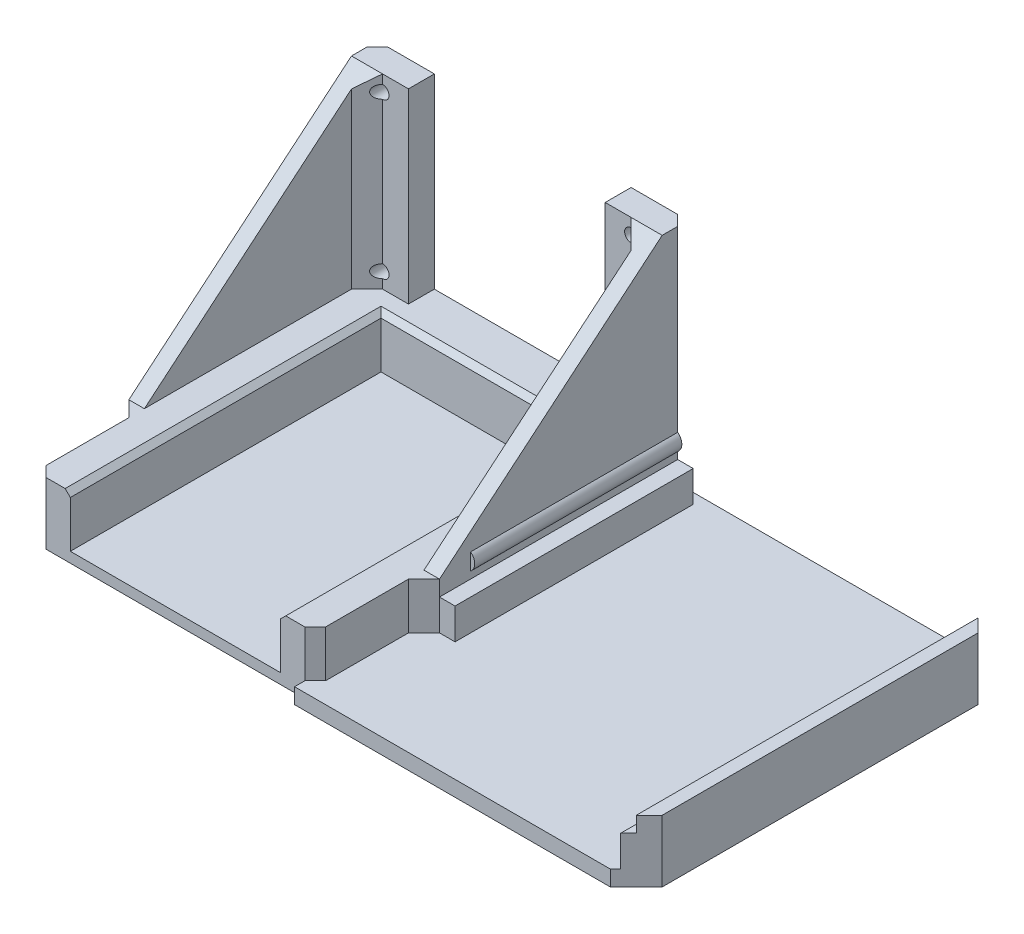
SolidWorks part; units mm, degrees
material "ABS"
ref_plane "Front Plane" through (0, 0, 0) normal (0, 0, 1) x (1, 0, 0)
ref_plane "Top Plane" through (0, 0, 0) normal (0, 1, 0) x (1, 0, 0)
ref_plane "Right Plane" through (0, 0, 0) normal (1, 0, 0) x (0, 0, -1)
sketch "Sketch1" plane through (0, 0, 0) normal (0, 0, 1) x (1, 0, 0)
  line L0 (-3, -3) -> (-3, 33)
  line L1 (0, 0) -> (5, 0) construction
  line L2 (0, 0) -> (0, 30) construction
  line L3 (0, 30) -> (5, 30) construction
  line L4 (48, 0) -> (48, 30) construction
  line L5 (-3, 33) -> (5, 33)
  line L6 (51, -3) -> (51, 33)
  line L7 (-3, -3) -> (5, -3)
  line L8 (43, 33) -> (51, 33)
  line L9 (-3, 33) -> (5, 33)
  line L10 (-3, 33) -> (-3, -3)
  line L11 (-3, -3) -> (5, -3)
  line L12 (5, 33) -> (5, -3)
  line L13 (51, 33) -> (43, 33)
  line L14 (51, 33) -> (51, -3)
  line L15 (51, -3) -> (43, -3)
  line L16 (43, 33) -> (43, -3)
  line L17 (-3, 33) -> (51, 33) construction
  line L18 (43, 30) -> (48, 30) construction
  line L19 (0, 30) -> (48, 30) construction
  line L20 (43, 0) -> (48, 0) construction
  line L21 (0, 0) -> (48, 0) construction
  line L22 (43, -3) -> (51, -3)
  line L23 (-3, -3) -> (51, -3) construction
  circle A0 centre (0, 30) radius 1.25
  circle A1 centre (48, 30) radius 1.25
  circle A2 centre (48, 0) radius 1.25
  circle A3 centre (0, 0) radius 1.25
  dimension "D3" = 2.5
  dimension "D1" = 30
  dimension "D2" = 48
  dimension "D7" = 8
  dimension "D8" = 8
  dimension "D6" = 3
  dimension "D4" = 2
  dimension "D5" = 2
extrude "Boss-Extrude1" add sketch "Sketch1" along normal blind 5 contours L12 L5 L0 L7 A3 A0 | L8 L16 L15 L6 A2 A1 region at (1.0353, 15, 0) region at (46.9647, 15, 0)
sketch "Sketch2" plane through (0, -3, 0) normal (0, -1, 0) x (1, 0, 0)
  line L1 (-3, 5) -> (51, 5)
  line L2 (-3, 5) -> (-3, 0)
  line L3 (-3, 0) -> (51, 0)
  line L4 (51, 5) -> (51, 0)
extrude "Boss-Extrude2" add sketch "Sketch2" along normal blind 12
sketch "Sketch4" plane through (0, 0, 5) normal (0, 0, 1) x (1, 0, 0)
  line L0 (51, -15) -> (-3, -15) construction
  line L1 (-3, -3) -> (51, -3)
  line L2 (-3, -3) -> (-3, -15)
  line L3 (-3, -15) -> (51, -15)
  line L4 (51, -3) -> (51, -15)
  line L6 (-3, -15) -> (-3, 33) construction
  line L7 (51, -15) -> (51, 33) construction
extrude "Boss-Extrude3" add sketch "Sketch4" along normal blind 64
sketch "Sketch5" plane through (0, -3, 0) normal (0, 1, 0) x (1, 0, 0)
  line L1 (3.7, -9) -> (44.3, -9)
  line L2 (3.7, -9) -> (3.7, -69.5)
  line L3 (3.7, -69.5) -> (44.3, -69.5)
  line L4 (44.3, -9) -> (44.3, -69.5)
  line L6 (24, -69) -> (24, -69.5) construction
  line L7 (51, -69) -> (-3, -69) construction
  line L8 (5, -5) -> (-3, -5) construction
  dimension "D1" = 40.6
  dimension "D2" = 60.5
  dimension "D3" = 4
extrude "Cut-Extrude1" cut sketch "Sketch5" against normal blind 10
sketch "Sketch7" plane through (-3, 0, 0) normal (-1, 0, 0) x (0, 0, 1)
  line L0 (0, 33) -> (0, -15)
  line L1 (0, -15) -> (0, 33) construction
  line L2 (0, -15) -> (48, -15)
  line L3 (69, -15) -> (0, -15) construction
  line L4 (48, -15) -> (48, -3)
  line L5 (69, -3) -> (5, -3) construction
  line L6 (48, -3) -> (5, 33)
  line L7 (5, 33) -> (0, 33)
extrude "Boss-Extrude4" add sketch "Sketch7" along normal blind 3
extrude "Boss-Extrude5" add sketch "Sketch7<2>" against normal blind 3 from surface starting at face at (51, 5, 24.6667)
sketch "Sketch7<2>" plane through (-3, 0, 0) normal (-1, 0, 0) x (0, 0, 1) same geometry as "Sketch7"
chamfer "Chamfer1" distance 2 angle 45 4 edges at (51, -9, 69) (-3, -9, 69) (54, 9, 0) (-6, 9, 0)
chamfer "Chamfer2" distance 1 angle 45 3 edges at (3.7, -3, 39) (24, -3, 9) (44.3, -3, 39)
chamfer "Chamfer3" distance 3 angle 45 4 edges at (51, -9, 48) (-3, -9, 48) (-3, 15, 5) (51, 15, 5)
sketch "Sketch8" plane through (0, -15, 0) normal (0, -1, 0) x (1, 0, 0)
  line L1 (115, 0) -> (49, 0)
  line L2 (115, 0) -> (115, 71)
  line L3 (115, 71) -> (49, 71)
  line L4 (49, 0) -> (49, 71)
  dimension "D1" = 66
  dimension "D2" = 71
extrude "Boss-Extrude6" add sketch "Sketch8" against normal blind 3
sketch "Sketch9" plane through (0, -12, 0) normal (0, 1, 0) x (1, 0, 0)
  line L0 (115, -71) -> (49, -71) construction
  line L1 (57, -2) -> (54, -2)
  line L2 (57, -2) -> (57, -48)
  line L3 (57, -48) -> (54, -48)
  line L4 (54, -2) -> (54, -48)
  line L5 (111, 0) -> (115, 0)
  line L6 (111, 0) -> (111, -71)
  line L7 (111, -71) -> (115, -71)
  line L8 (115, 0) -> (115, -71)
  line L9 (54, -2) -> (54, -48) construction
  line L10 (115, 0) -> (115, -71) construction
  dimension "D1" = 3
  dimension "D2" = 4
extrude "Boss-Extrude7" add sketch "Sketch9" along normal blind 6
sketch "Sketch11" plane through (0, 0, 2) normal (0, 0, -1) x (-1, 0, 0)
  line L10 (-54, -1.45) -> (-54, -4.65)
  arc A1 (-54, -4.65) -> (-54, -1.45) centre (-52.8, -3.05) cw
extrude "Boss-Extrude8" add sketch "Sketch11" against normal blind 40
sketch "Sketch12" plane through (0, -6, 0) normal (0, 1, 0) x (1, 0, 0)
  line L0 (111, -71) -> (115, -71) construction
  line L1 (112.5, 0) -> (115, 0)
  line L2 (112.5, 0) -> (112.5, -71)
  line L3 (112.5, -71) -> (115, -71)
  line L4 (115, 0) -> (115, -71)
  line L5 (115, -71) -> (115, 0) construction
  dimension "D1" = 2.5
extrude "Boss-Extrude9" add sketch "Sketch12" along normal blind 3
chamfer "Chamfer4" distance 5 angle 45 2 edges at (115, -9, 0) (115, -9, 71)
